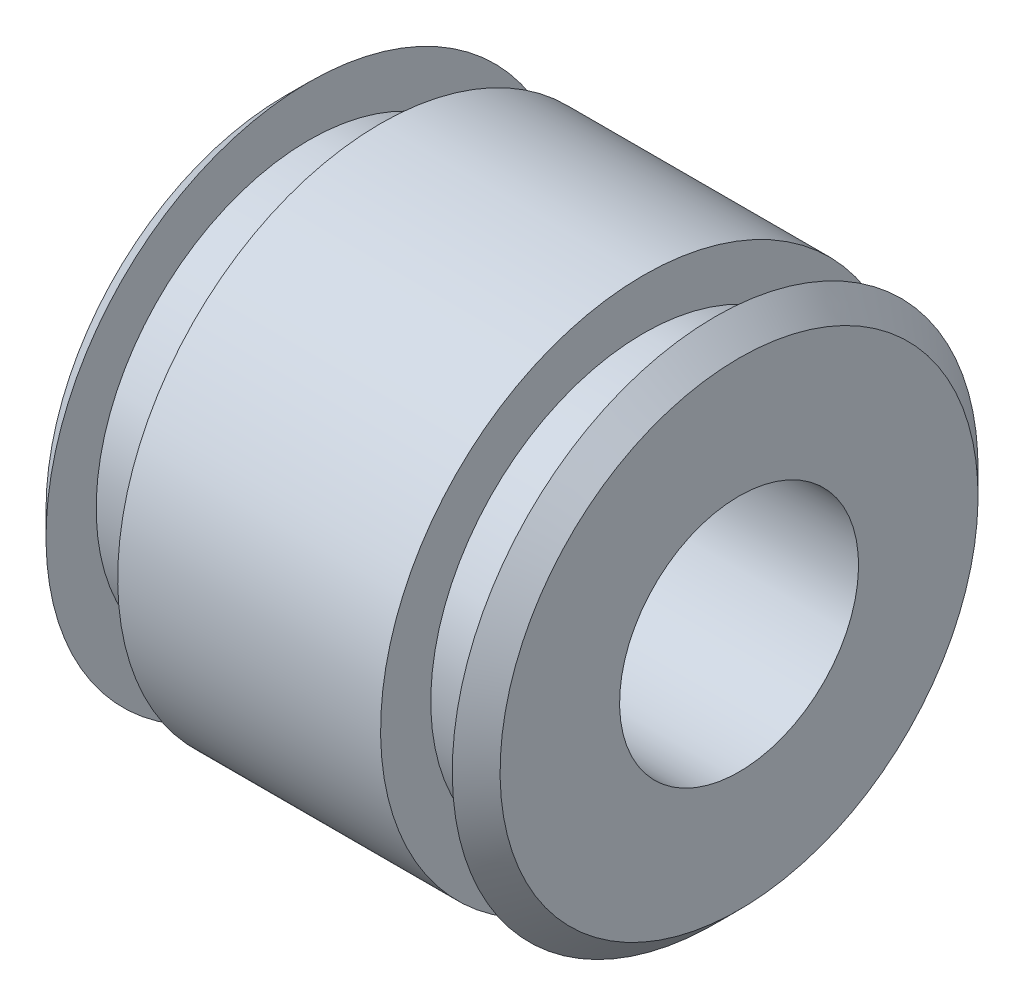
SolidWorks part; units mm, degrees
material "Acciaio al carbonio semplice"
ref_plane "Piano frontale" through (0, 0, 0) normal (0, 0, 1) x (1, 0, 0)
ref_plane "Piano superiore" through (0, 0, 0) normal (0, 1, 0) x (1, 0, 0)
ref_plane "Piano destro" through (0, 0, 0) normal (1, 0, 0) x (0, 0, -1)
sketch "Schizzo1" plane through (0, 0, 0) normal (0, 0, 1) x (1, 0, 0)
  line L0 (0, 0) -> (0, 11)
  line L2 (19, 11) -> (19, 0)
  line L3 (19, 0) -> (0, 0) construction
  line L8 (18, 11) -> (19, 11)
  line L9 (0, 0) -> (19, 0) construction
  line L10 (15, 11) -> (15, 8.9)
  line L11 (15, 8.9) -> (18, 8.9)
  line L12 (18, 8.9) -> (18, 11)
  line L13 (19, 0) -> (0, 0)
  line L15 (1, 8.9) -> (4, 8.9)
  line L16 (4, 8.9) -> (4, 11)
  line L17 (4, 11) -> (15, 11)
  line L18 (0, 11) -> (1, 11)
  line L19 (1, 11) -> (1, 8.9)
  line L20 (0, 0) -> (-4.0571, 0) construction
  point P3 (4, 8.1346)
  dimension "D1" = 2.1
  dimension "D2" = 3
  dimension "D3" = 1
  dimension "D4" = 22
  dimension "D5" = 19
  dimension "D6" = 1
revolve "Rivoluzione1" add sketch "Schizzo1" angle 360 about L3
sketch "Schizzo2" plane through (19, 0, 0) normal (1, 0, 0) x (0, 0, -1)
  circle A0 centre (0, 0) radius 5
  dimension "D1" = 10
extrude "Taglio-Estrusione1" cut sketch "Schizzo2" against normal blind 16
chamfer "Smusso1" distance 1 angle 45 2 edges at (19, 11, 0) (0, 11, 0)
